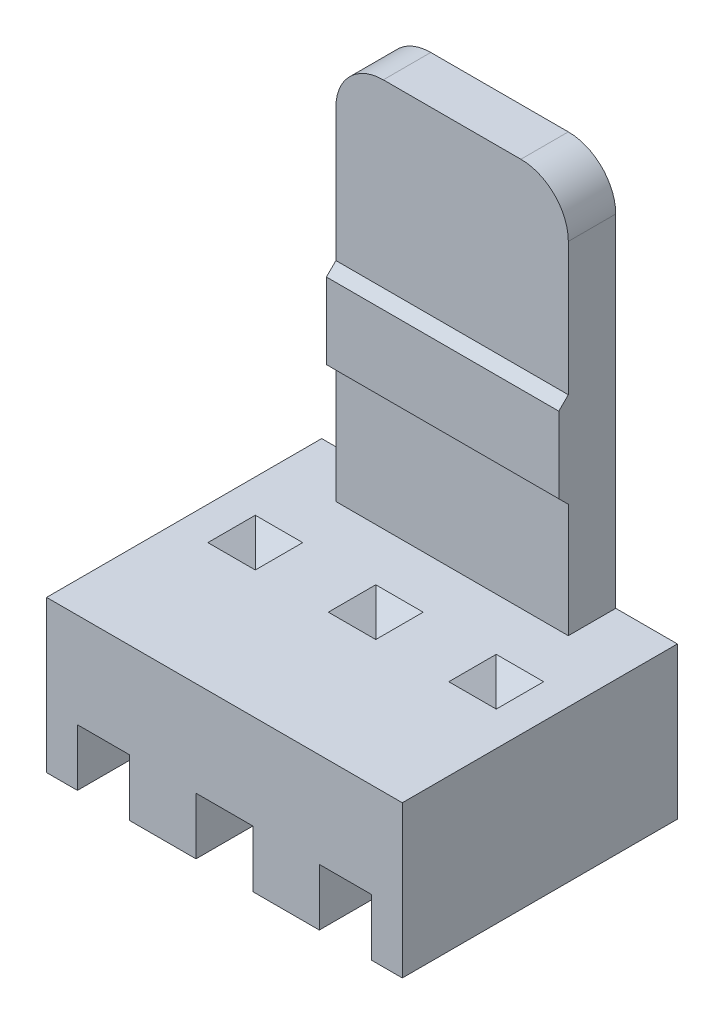
SolidWorks part; units mm, degrees
ref_plane "Спереди" through (0, 0, 0) normal (0, 0, 1) x (1, 0, 0)
ref_plane "Сверху" through (0, 0, 0) normal (0, 1, 0) x (1, 0, 0)
ref_plane "Справа" through (0, 0, 0) normal (1, 0, 0) x (0, 0, -1)
sketch "Эскиз1" plane through (0, 0, 0) normal (0, 0, 1) x (1, 0, 0)
  line L0 (0, 0) -> (0, 3.2)
  line L1 (0, 3.2) -> (7.5, 3.2)
  line L2 (5.75, 0) -> (4.35, 0)
  line L3 (4.35, 0) -> (4.35, 1.2)
  line L4 (4.35, 1.2) -> (3.15, 1.2)
  line L5 (3.15, 1.2) -> (3.15, 0)
  line L6 (3.15, 0) -> (1.75, 0)
  line L7 (1.75, 0) -> (1.75, 1.2)
  line L8 (1.75, 1.2) -> (0.65, 1.2)
  line L9 (0.65, 1.2) -> (0.65, 0)
  line L10 (0.65, 0) -> (0, 0)
  line L11 (7.5, 0) -> (7.5, 3.2)
  line L12 (5.75, 1.2) -> (6.85, 1.2)
  line L13 (6.85, 1.2) -> (6.85, 0)
  line L14 (6.85, 0) -> (7.5, 0)
  line L15 (5.75, 0) -> (5.75, 1.2)
  line L16 (3.75, 1.2) -> (3.75, 3.2) construction
  dimension "D1" = 1.4
  dimension "D3" = 1.1
  dimension "D4" = 1.4
  dimension "D5" = 1.2
  dimension "D6" = 1.1
  dimension "D7" = 1.2
  dimension "D8" = 3.2
  dimension "D9" = 7.5
extrude "Бобышка-Вытянуть1" add sketch "Эскиз1" along normal blind 5.8
sketch "Эскиз2" plane through (0, 3.2, 0) normal (0, 1, 0) x (1, 0, 0)
  line L0 (7.5, 0) -> (0, 0) construction
  line L1 (1.3, 0) -> (6.2, 0)
  line L2 (1.3, 0) -> (1.3, -1)
  line L3 (1.3, -1) -> (6.2, -1)
  line L4 (6.2, 0) -> (6.2, -1)
  line L5 (3.75, 0) -> (3.75, -5.8) construction
  line L6 (7.5, -5.8) -> (0, -5.8) construction
  dimension "D1" = 4.9
  dimension "D2" = 1
extrude "Бобышка-Вытянуть2" add sketch "Эскиз2" along normal blind 8.2
sketch "Эскиз3" plane through (0, 0, 1) normal (0, 0, 1) x (1, 0, 0)
  line L0 (1.3, 11.4) -> (1.3, 3.2) construction
  line L1 (1.3, 5.6) -> (6.2, 5.6)
  line L2 (1.3, 5.6) -> (1.3, 7.6)
  line L3 (1.3, 7.6) -> (6.2, 7.6)
  line L4 (6.2, 5.6) -> (6.2, 7.6)
  line L5 (6.2, 11.4) -> (6.2, 3.2) construction
  line L6 (1.3, 3.2) -> (6.2, 3.2) construction
  dimension "D1" = 2.4
  dimension "D2" = 2
extrude "Бобышка-Вытянуть3" add sketch "Эскиз3" along normal blind 0.2
chamfer "Фаска1" distance 0.2 angle 45 2 edges at (3.75, 5.6, 1.2) (3.75, 7.6, 1.2)
fillet "Скругление1" radius 1 2 edges at (1.3, 11.4, 0.5) (6.2, 11.4, 0.5)
sketch "Эскиз4" plane through (0, 3.2, 0) normal (0, 1, 0) x (1, 0, 0)
  line L0 (1.3, 0) -> (0, 0) construction
  line L1 (0.7, -2.1) -> (1.7, -2.1)
  line L2 (0.7, -2.1) -> (0.7, -3.1)
  line L3 (0.7, -3.1) -> (1.7, -3.1)
  line L4 (1.7, -2.1) -> (1.7, -3.1)
  line L5 (0, -5.8) -> (0, 0) construction
  dimension "D1" = 1
  dimension "D2" = 1
  dimension "D3" = 2.1
  dimension "D4" = 0.7
extrude "Вырез-Вытянуть1" cut sketch "Эскиз4" against normal blind 0.5 draft 44
pattern_linear "Линейный массив1" count 3 spacing 2.54 along (1, 0, 0) of "Вырез-Вытянуть1"
